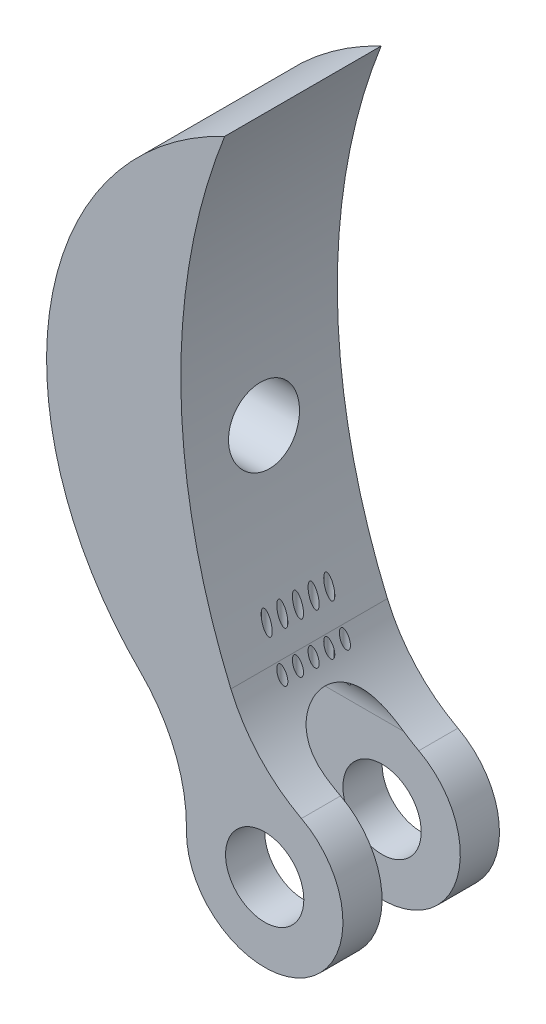
SolidWorks part; units mm, degrees
ref_plane "前视基准面" through (0, 0, 0) normal (0, 0, 1) x (1, 0, 0)
ref_plane "上视基准面" through (0, 0, 0) normal (0, 1, 0) x (1, 0, 0)
ref_plane "右视基准面" through (0, 0, 0) normal (1, 0, 0) x (0, 0, -1)
other "Configuration Table"
sketch "Sketch1" plane through (0, 0, 0) normal (0, 0, 1) x (1, 0, 0)
  line L0 (-5, 0) -> (-5, 5)
  line L1 (0, 0) -> (0, 5)
  line L2 (0, 5) -> (-5, 5)
  circle A0 centre (0, 0) radius 5
  circle A1 centre (0, 0) radius 2.5
  dimension "D1" = 5
  dimension "D2" = 10
  dimension "D3" = 5
extrude "Boss-Extrude1" add sketch "Sketch1" along normal mid plane 10 contours A0 L1 L2 L0 | A1 A0 region at (-3.8832, 3.8832, 0) region at (-3.4355, 3.4355, 0)
sketch "Sketch2" plane through (0, 0, 5) normal (0, 0, 1) x (1, 0, 0)
  line L0 (0, 5) -> (-5, 5) construction
  line L3 (0, 5) -> (6.0641, 21.6609) construction
  line L4 (0, 5) -> (34.641, 25) construction
  line L5 (0, 7.5) -> (0, 5) construction
  line L6 (-5, 5) -> (0, 5)
  arc A1 (-5, 0) -> (0, 5) centre (0, 0) ccw construction
  arc A2 (-5, 5) -> (-2.557, 39.7075) centre (6.0641, 21.6609) cw
  arc A3 (-2.557, 39.7075) -> (0, 5) centre (34.641, 25) ccw
  dimension "D1" = 40
  dimension "D2" = 20
  dimension "D3" = 20
  dimension "D4" = 40
extrude "Boss-Extrude2" add sketch "Sketch2" against normal up to surface (10 mm away) up to face at (-1.3215, 1.3215, -5)
fillet "Fillet2" radius 10 1 edges at (-5, 5, 0)
fillet "Fillet3" radius 10 1 edges at (0, 5, 0)
sketch "Sketch3" plane through (0, 0, 0) normal (1, 0, 0) x (0, 0, -1)
  line L2 (-5, -5) -> (5, -5) construction
  line L3 (0, -5) -> (0, 20) construction
  circle A0 centre (0, 20) radius 2.25
  dimension "D1" = 4.5
  dimension "D2" = 25
extrude "Cut-Extrude1" cut sketch "Sketch3" against normal through all
sketch "Sketch5" plane through (0, 0, 0) normal (1, 0, 0) x (0, 0, -1)
  line L1 (-2.5, -7.5) -> (2.5, -7.5)
  line L2 (-2.5, -7.5) -> (-2.5, 7.5)
  line L3 (-2.5, 7.5) -> (2.5, 7.5)
  line L4 (2.5, -7.5) -> (2.5, 7.5)
  line L5 (-2.5, -7.5) -> (2.5, 7.5) construction
  line L6 (-2.5, 7.5) -> (2.5, -7.5) construction
  point P0 (0, 0)
  dimension "D1" = 5
  dimension "D2" = 15
extrude "Cut-Extrude2" cut sketch "Sketch5" against normal through all both and the other way through all
sketch "Sketch6" plane through (0, 7.5, 0) normal (0, -1, 0) x (1, 0, 0)
  line L0 (-1.145, 0) -> (-8.0593, 0) construction
  line L1 (-1.145, 2.5) -> (-1.145, -2.5) construction
  line L2 (-8.0593, 2.5) -> (-8.0593, -2.5) construction
  line L3 (-8.0593, 0) -> (-4.6021, 0) construction
  line L4 (-4.6021, 0) -> (-4.6021, 2) construction
  line L7 (-4.6021, 2) -> (-1.145, 2) construction
  line L8 (-1.145, 2) -> (-2.8736, 2) construction
  circle A0 centre (-2.8736, 2) radius 0.25
  circle A1 centre (-1.8736, 2) radius 0.25
  circle A2 centre (-3.8736, 2) radius 0.25
  circle A3 centre (-4.8736, 2) radius 0.25
  circle A4 centre (-5.8736, 2) radius 0.25
  circle A5 centre (-6.8736, 2) radius 0.25
  circle A6 centre (-6.8736, 1) radius 0.25
  circle A7 centre (-5.8736, 1) radius 0.25
  circle A8 centre (-4.8736, 1) radius 0.25
  circle A9 centre (-3.8736, 1) radius 0.25
  circle A10 centre (-2.8736, 1) radius 0.25
  circle A11 centre (-1.8736, 1) radius 0.25
  circle A12 centre (-6.8736, 0) radius 0.25
  circle A13 centre (-5.8736, 0) radius 0.25
  circle A14 centre (-4.8736, 0) radius 0.25
  circle A15 centre (-3.8736, 0) radius 0.25
  circle A16 centre (-2.8736, 0) radius 0.25
  circle A17 centre (-1.8736, 0) radius 0.25
  circle A18 centre (-6.8736, -1) radius 0.25
  circle A19 centre (-5.8736, -1) radius 0.25
  circle A20 centre (-4.8736, -1) radius 0.25
  circle A21 centre (-3.8736, -1) radius 0.25
  circle A22 centre (-2.8736, -1) radius 0.25
  circle A23 centre (-1.8736, -1) radius 0.25
  circle A24 centre (-6.8736, -2) radius 0.25
  circle A25 centre (-5.8736, -2) radius 0.25
  circle A26 centre (-4.8736, -2) radius 0.25
  circle A27 centre (-3.8736, -2) radius 0.25
  circle A28 centre (-2.8736, -2) radius 0.25
  circle A29 centre (-1.8736, -2) radius 0.25
  dimension "D1" = 0.5
  dimension "D3" = 1
  dimension "D5" = 1
  dimension "D6" = 2
  dimension "D8" = 1
  dimension "D2" = 2
  dimension "D4" = 5
  dimension "D7" = 5
extrude "Cut-Extrude3" cut sketch "Sketch6" against normal blind 5
fillet "Fillet5" radius 2.5 2 edges at (-4.6021, 7.5, -2.5) (-4.6021, 7.5, 2.5)
